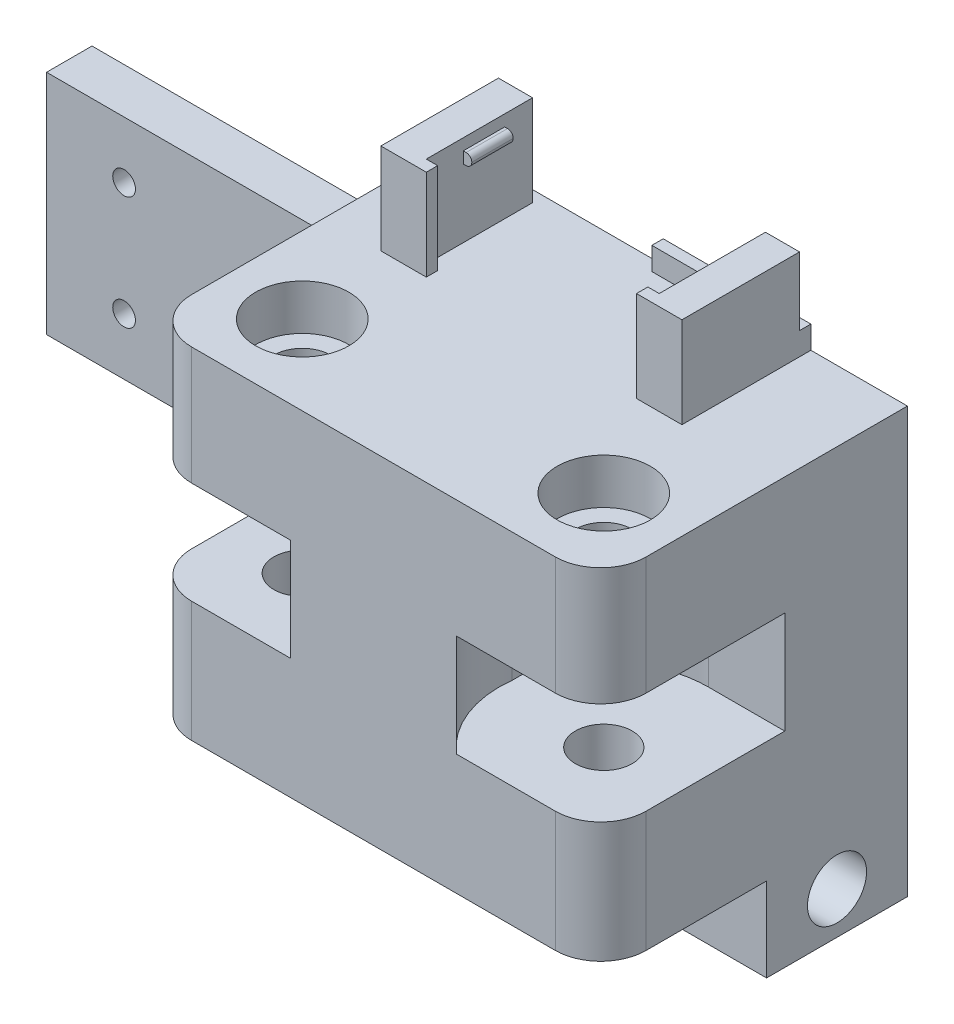
SolidWorks part; units mm, degrees
ref_plane "Front Plane" through (0, 0, 0) normal (0, 0, 1) x (1, 0, 0)
ref_plane "Top Plane" through (0, 0, 0) normal (0, 1, 0) x (1, 0, 0)
ref_plane "Right Plane" through (0, 0, 0) normal (1, 0, 0) x (0, 0, -1)
sketch "Sketch1" plane through (0, 0, 0) normal (0, 1, 0) x (1, 0, 0)
  line L1 (-22.8462, -9.1868) -> (17.1538, -9.1868)
  line L2 (-22.8462, -9.1868) -> (-22.8462, 17.8132)
  line L3 (-22.8462, 17.8132) -> (17.1538, 17.8132)
  line L4 (17.1538, -9.1868) -> (17.1538, 17.8132)
  dimension "D1" = 27
  dimension "D2" = 40
extrude "Boss-Extrude1" add sketch "Sketch1" along normal blind 30
sketch "Sketch2" plane through (0, 0, -17.8132) normal (0, 0, -1) x (-1, 0, 0)
  line L0 (2.8462, 30) -> (2.8462, 0) construction
  line L1 (-8.0864, 4) -> (-0.2064, 4)
  line L2 (-0.2064, 4) -> (-0.2064, 7)
  line L3 (-0.2064, 7) -> (-2.8664, 7)
  line L4 (-2.8664, 7) -> (-2.8664, 8.0087)
  line L5 (-2.8664, 8.0087) -> (-0.2538, 10.6287)
  line L6 (-0.2538, 10.6287) -> (5.9462, 10.6287)
  line L7 (-17.1538, 30) -> (22.8462, 30) construction
  line L8 (-17.1538, 0) -> (22.8462, 0) construction
  line L9 (-8.0864, 4) -> (-8.0864, 26)
  line L10 (-8.0864, 26) -> (-0.2064, 26)
  line L11 (-0.2064, 26) -> (-0.2064, 23)
  line L12 (-0.2064, 23) -> (-2.8664, 23)
  line L13 (-2.8664, 23) -> (-2.8664, 21.9913)
  line L14 (-2.8664, 21.9913) -> (-0.2464, 19.3787)
  line L15 (-0.2464, 19.3787) -> (5.9536, 19.3787)
  line L16 (-17.1538, 15) -> (22.8462, 15) construction
  line L17 (-17.1538, 30) -> (-17.1538, 0) construction
  line L18 (22.8462, 30) -> (22.8462, 0) construction
  line L19 (5.9387, 19.3787) -> (-0.2613, 19.3787)
  line L20 (8.5587, 21.9913) -> (5.9387, 19.3787)
  line L21 (8.5587, 23) -> (8.5587, 21.9913)
  line L22 (5.8987, 23) -> (8.5587, 23)
  line L23 (5.8987, 26) -> (5.8987, 23)
  line L24 (13.7787, 26) -> (5.8987, 26)
  line L25 (13.7787, 4) -> (13.7787, 26)
  line L26 (8.5587, 8.0087) -> (5.9462, 10.6287)
  line L27 (8.5587, 7) -> (8.5587, 8.0087)
  line L28 (5.8987, 7) -> (8.5587, 7)
  line L29 (5.8987, 4) -> (5.8987, 7)
  line L30 (13.7787, 4) -> (5.8987, 4)
  point P26 (-8.0864, 15)
  point P27 (2.8462, 15)
  point P37 (2.8462, 10.6287)
  dimension "D1" = 6.2
  dimension "D2" = 2.62
  dimension "D3" = 3.7
  dimension "D4" = 8.75
  dimension "D5" = 7.88
  dimension "D6" = 22
  dimension "D7" = 5.22
  dimension "D8" = 3
  dimension "D9" = 90
extrude "Cut-Extrude1" cut sketch "Sketch2" against normal blind 10 contours L30 L25 L24 L23 L22 L21 L20 L15 L14 L13 L12 L11 L10 L9 L1 L2 L3 L4 L5 L6 L26 L27 L28 L29 region at (-2.8462, 15.0011, -17.8132)
sketch "Sketch3" plane through (0, 0, 0) normal (0, -1, 0) x (1, 0, 0)
  line L0 (-22.8462, 9.1868) -> (17.1538, 9.1868) construction
  line L1 (17.1538, 9.1868) -> (17.1538, -17.8132) construction
  line L2 (-2.8462, 9.1868) -> (-2.8462, -17.8132) construction
  line L3 (17.1538, -17.8132) -> (-22.8462, -17.8132) construction
  circle A0 centre (10.4238, 2.1868) radius 2.5
  circle A2 centre (-16.1162, 2.1868) radius 2.5
  dimension "D1" = 5
  dimension "D3" = 7
  dimension "D4" = 6.73
extrude "Cut-Extrude2" cut sketch "Sketch3" against normal blind 30
sketch "Sketch8" plane through (0, 0, 0) normal (0, -1, 0) x (1, 0, 0)
  line L0 (4.4539, 9.1868) -> (17.1538, 9.1868)
  line L1 (-22.8462, 9.1868) -> (17.1538, 9.1868) construction
  line L2 (17.1538, 9.1868) -> (17.1538, -7.0132)
  line L3 (17.1538, 9.1868) -> (17.1538, -17.8132) construction
  line L4 (17.1538, -7.0132) -> (10.4238, -7.0132)
  line L6 (-2.8462, -17.8132) -> (-2.8462, 9.1868) construction
  line L7 (17.1538, -17.8132) -> (-22.8462, -17.8132) construction
  line L8 (-22.8462, -7.0132) -> (-16.1162, -7.0132)
  line L9 (-22.8462, 9.1868) -> (-22.8462, -7.0132)
  line L10 (-10.1462, 9.1868) -> (-22.8462, 9.1868)
  arc A0 (10.4238, -7.0132) -> (4.4539, 9.1868) centre (10.4238, 2.1868) cw
  arc A1 (-16.1162, -7.0132) -> (-10.1462, 9.1868) centre (-16.1162, 2.1868) ccw
  circle M6 centre (10.4238, 2.1868) radius 2.5
  circle M7 centre (-16.1162, 2.1868) radius 2.5
  line M8 (-22.8462, 9.1868) -> (-22.8462, -17.8132)
  line M10 (17.1538, -17.8132) -> (17.1538, 9.1868)
  line M11 (17.1538, 9.1868) -> (-22.8462, 9.1868)
  dimension "D1" = 9.2
  dimension "D2" = 6.73
extrude "Cut-Extrude5" cut sketch "Sketch8" against normal blind 9 from offset 10.62 contours A0 L4 M10 M11 M6 | M6 | L8 A1 M11 M8 M7 | M7 region at (10.8039, 0, 8.9596) region at (-7.6968, 0, -0.9158) region at (10.4238, 0, 2.1868) region at (-16.1162, 0, 2.1868) offset against normal yes
sketch "Sketch10" plane through (8.0864, 0, 0) normal (-1, 0, 0) x (0, 0, 1)
  line L0 (-17.8132, 30) -> (-17.8132, 0) construction
  line L1 (-17.8132, 18.82) -> (2.1868, 18.82)
  line L2 (-17.8132, 18.82) -> (-17.8132, 10.62)
  line L3 (-17.8132, 10.62) -> (2.1868, 10.62)
  line L4 (2.1868, 18.82) -> (2.1868, 10.62)
  line L5 (-17.8132, 30) -> (9.1868, 30) construction
  dimension "D1" = 20
  dimension "D2" = 11.18
  dimension "D3" = 8.2
extrude "Cut-Extrude7" cut sketch "Sketch10" along normal blind 6.8
sketch "Sketch12" plane through (-13.7787, 0, 0) normal (1, 0, 0) x (0, 0, -1)
  line L1 (17.8132, 18.82) -> (-2.1868, 18.82)
  line L2 (17.8132, 18.82) -> (17.8132, 10.62)
  line L3 (17.8132, 10.62) -> (-2.1868, 10.62)
  line L4 (-2.1868, 18.82) -> (-2.1868, 10.62)
  line L5 (-9.1868, 30) -> (17.8132, 30) construction
  dimension "D1" = 20
  dimension "D2" = 8.2
  dimension "D3" = 11.18
extrude "Cut-Extrude10" cut sketch "Sketch12" along normal blind 6.8
fillet "Fillet1" radius 4 4 edges at (17.1538, 5.31, 9.1868) (17.1538, 24.81, 9.1868) (-22.8462, 5.31, 9.1868) (-22.8462, 24.81, 9.1868)
sketch "Sketch13" plane through (17.1538, 0, 0) normal (1, 0, 0) x (0, 0, -1)
  line L0 (-5.1868, 0) -> (17.8132, 0) construction
  line L1 (17.8132, 30) -> (17.8132, 0) construction
  line L3 (17.8132, 0) -> (5.4132, 0)
  line L4 (17.8132, 0) -> (17.8132, -7.4)
  line L5 (17.8132, -7.4) -> (5.4132, -7.4)
  line L6 (5.4132, 0) -> (5.4132, -7.4)
  circle A0 centre (11.6132, -3.7) radius 2.6
  dimension "D1" = 6.2
  dimension "D2" = 3.7
  dimension "D3" = 5.2
  dimension "D4" = 12.4
  dimension "D5" = 7.4
extrude "Boss-Extrude2" add sketch "Sketch13" against normal up to surface (40 mm away) up to face at (-22.8462, 15.06, -3.6132)
sketch "Sketch14" plane through (0, 0, -5.4132) normal (0, 0, 1) x (1, 0, 0)
  line L0 (-22.8462, -7.4) -> (17.1538, -7.4) construction
  line L1 (-12.8462, -7.4) -> (7.1538, -7.4)
  line L2 (-12.8462, -7.4) -> (-12.8462, 0)
  line L3 (-12.8462, 0) -> (7.1538, 0)
  line L4 (7.1538, -7.4) -> (7.1538, 0)
  line L5 (-18.8462, 0) -> (13.1538, 0) construction
  line L7 (17.1538, 0) -> (17.1538, -7.4) construction
  dimension "D1" = 20
  dimension "D2" = 10
extrude "Cut-Extrude11" cut sketch "Sketch14" against normal up to next
sketch "Sketch15" plane through (0, 30, 0) normal (0, 1, 0) x (1, 0, 0)
  line L0 (-2.8462, 17.8132) -> (-2.8462, -9.1868) construction
  line L13 (17.1538, 17.8132) -> (-22.8462, 17.8132) construction
  line L14 (-18.8462, -9.1868) -> (13.1538, -9.1868) construction
  circle A4 centre (-16.1162, -2.1868) radius 4.1
  circle A5 centre (10.4238, -2.1868) radius 4.1
  dimension "D1" = 8.2
extrude "Cut-Extrude12" cut sketch "Sketch15" against normal blind 4
sketch "Sketch16" plane through (0, 0, 0) normal (0, -1, 0) x (1, 0, 0)
  line L1 (-13.749, -1.9132) -> (-11.3819, 2.1868)
  line L2 (-11.3819, 2.1868) -> (-13.749, 6.2868)
  line L3 (-13.749, 6.2868) -> (-18.4833, 6.2868)
  line L4 (-18.4833, 6.2868) -> (-20.8504, 2.1868)
  line L5 (-20.8504, 2.1868) -> (-18.4833, -1.9132)
  line L6 (-18.4833, -1.9132) -> (-13.749, -1.9132)
  line L7 (12.791, -1.9132) -> (15.1581, 2.1868)
  line L8 (15.1581, 2.1868) -> (12.791, 6.2868)
  line L9 (12.791, 6.2868) -> (8.0567, 6.2868)
  line L10 (8.0567, 6.2868) -> (5.6896, 2.1868)
  line L11 (5.6896, 2.1868) -> (8.0567, -1.9132)
  line L12 (8.0567, -1.9132) -> (12.791, -1.9132)
  circle A0 centre (10.4238, 2.1868) radius 2.5 construction
  circle A1 centre (-16.1162, 2.1868) radius 2.5 construction
  circle A2 centre (10.4238, 2.1868) radius 2.5
  circle A3 centre (-16.1162, 2.1868) radius 2.5
  circle A4 centre (-16.1162, 2.1868) radius 4.1 construction
  circle A5 centre (10.4238, 2.1868) radius 4.1 construction
  dimension "D1" = 8.2
  dimension "D2" = 8.2
extrude "Cut-Extrude13" cut sketch "Sketch16" against normal blind 4
sketch "Sketch17" plane through (0, 30, 0) normal (0, 1, 0) x (1, 0, 0)
  line L1 (8.6538, 16.8132) -> (5.6538, 16.8132)
  line L2 (8.6538, 16.8132) -> (8.6538, 7.4632)
  line L3 (8.6538, 7.4632) -> (5.6538, 7.4632)
  line L4 (-18.8462, -9.1868) -> (13.1538, -9.1868)
  line L5 (17.1538, -5.1868) -> (17.1538, 17.8132)
  line L6 (17.1538, 17.8132) -> (-22.8462, 17.8132)
  line L7 (-22.8462, 17.8132) -> (-22.8462, -5.1868)
  line L8 (-18.8462, -9.1868) -> (13.1538, -9.1868)
  line L9 (17.1538, -5.1868) -> (17.1538, 17.8132)
  line L10 (17.1538, 17.8132) -> (-22.8462, 17.8132)
  line L11 (-22.8462, 17.8132) -> (-22.8462, -5.1868)
  line L12 (5.6538, 16.8132) -> (5.6538, 7.4632)
  line L13 (-14.8462, 16.8132) -> (-17.8462, 16.8132)
  line L14 (-14.8462, 16.8132) -> (-14.8462, 7.4632)
  line L15 (-14.8462, 7.4632) -> (-17.8462, 7.4632)
  line L16 (-17.8462, 16.8132) -> (-17.8462, 7.4632)
  line L17 (8.6538, 7.4632) -> (4.6538, 7.4632)
  line L18 (8.6538, 7.4632) -> (8.6538, 6.4632)
  line L19 (8.6538, 6.4632) -> (4.6538, 6.4632)
  line L20 (4.6538, 7.4632) -> (4.6538, 6.4632)
  line L21 (-17.8462, 7.4632) -> (-13.8462, 7.4632)
  line L22 (-17.8462, 7.4632) -> (-17.8462, 6.4632)
  line L23 (-17.8462, 6.4632) -> (-13.8462, 6.4632)
  line L24 (-13.8462, 7.4632) -> (-13.8462, 6.4632)
  arc A2 (13.1538, -9.1868) -> (17.1538, -5.1868) centre (13.1538, -5.1868) ccw
  arc A3 (-22.8462, -5.1868) -> (-18.8462, -9.1868) centre (-18.8462, -5.1868) ccw
  arc A4 (13.1538, -9.1868) -> (17.1538, -5.1868) centre (13.1538, -5.1868) ccw
  arc A5 (-22.8462, -5.1868) -> (-18.8462, -9.1868) centre (-18.8462, -5.1868) ccw
  line M30 (17.1538, 17.8132) -> (-22.8462, 17.8132)
  dimension "D2" = 9.35
  dimension "D3" = 3
  dimension "D4" = 3
  dimension "D5" = 20.5
  dimension "D6" = 5
  dimension "D7" = 1
  dimension "D8" = 1
  dimension "D9" = 4
  dimension "D10" = 1
  dimension "D11" = 1
  dimension "D1" = 0
extrude "Boss-Extrude3" add sketch "Sketch17" along normal blind 8 contours L12 L3 L2 M30 | L10 L16 L15 L14 | L24 L21 L15 L22 L23 | L17 L20 L19 L18 L3 region at (7.1538, 30, -12.1382) region at (6.6538, 30, -6.9632) region at (-16.3462, 30, -12.1382) region at (-15.8462, 30, -6.9632)
sketch "Sketch20" plane through (0, 38, 0) normal (0, 1, 0) x (1, 0, 0)
  line L0 (5.6538, 16.8132) -> (5.6538, 7.4632) construction
  line L1 (5.6538, 14.3623) -> (4.9038, 14.3623)
  line L2 (5.6538, 14.3623) -> (5.6538, 10.716)
  line L3 (5.6538, 10.716) -> (4.9038, 10.716)
  line L4 (4.9038, 14.3623) -> (4.9038, 10.716)
  line L5 (-14.8462, 16.8132) -> (-14.8462, 7.4632) construction
  line L6 (-14.8462, 14.3623) -> (-14.0962, 14.3623)
  line L7 (-14.8462, 14.3623) -> (-14.8462, 10.716)
  line L8 (-14.8462, 10.716) -> (-14.0962, 10.716)
  line L9 (-14.0962, 14.3623) -> (-14.0962, 10.716)
  dimension "D1" = 0.75
  dimension "D2" = 0.75
extrude "Boss-Extrude4" add sketch "Sketch20" along normal blind 1 from offset 2 offset against normal yes
fillet "Fillet2" radius 0.5 4 edges at (-14.0962, 36, -12.5391) (4.9038, 36, -12.5391) (-14.0962, 37, -12.5391) (4.9038, 37, -12.5391)
sketch "Sketch22" plane through (0, 0, -17.8132) normal (0, 0, -1) x (-1, 0, 0)
  line L1 (-8.6538, 32) -> (4.3462, 32)
  line L2 (-8.6538, 32) -> (-8.6538, 30)
  line L3 (-8.6538, 30) -> (4.3462, 30)
  line L4 (4.3462, 32) -> (4.3462, 30)
  line L7 (-5.6538, 38) -> (-5.6538, 30) construction
  line L8 (-5.6538, 38) -> (-5.6538, 30)
  line L9 (-17.1538, 30) -> (22.8462, 30) construction
  line L11 (-8.6538, 38) -> (-8.6538, 30) construction
  point P6 (0, 0)
  dimension "D1" = 2
  dimension "D2" = 13
extrude "Boss-Extrude6" add sketch "Sketch22" along normal blind 1 from surface contours L8 L1 L2 L3 | L1 L8 L3 L4 region at (7.1538, 31, -17.8132) region at (0.6538, 31, -17.8132) starting at face at (7.1538, 34, -16.8132)
sketch "Sketch23" plane through (-22.8462, 0, 0) normal (-1, 0, 0) x (0, 0, 1)
  line L0 (-17.8132, 30) -> (-17.8132, -7.4) construction
  line L1 (-17.8132, 21.5555) -> (-13.8132, 21.5555)
  line L2 (-17.8132, 21.5555) -> (-17.8132, 1.5555)
  line L3 (-17.8132, 1.5555) -> (-13.8132, 1.5555)
  line L4 (-13.8132, 21.5555) -> (-13.8132, 1.5555)
  dimension "D1" = 20
  dimension "D2" = 4
extrude "Boss-Extrude7" add sketch "Sketch23" along normal blind 31.778
sketch "Sketch25" plane through (0, 0, -17.8132) normal (0, 0, -1) x (-1, 0, 0)
  line L0 (54.6242, 1.5555) -> (22.8462, 1.5555) construction
  line L1 (54.6242, 21.5555) -> (54.6242, 1.5555) construction
  circle A0 centre (47.7982, 16.5555) radius 1
  circle A1 centre (47.7982, 6.5555) radius 1
  dimension "D1" = 2
  dimension "D4" = 6.826
  dimension "D2" = 10
  dimension "D3" = 5
extrude "Cut-Extrude15" cut sketch "Sketch25" against normal up to next
